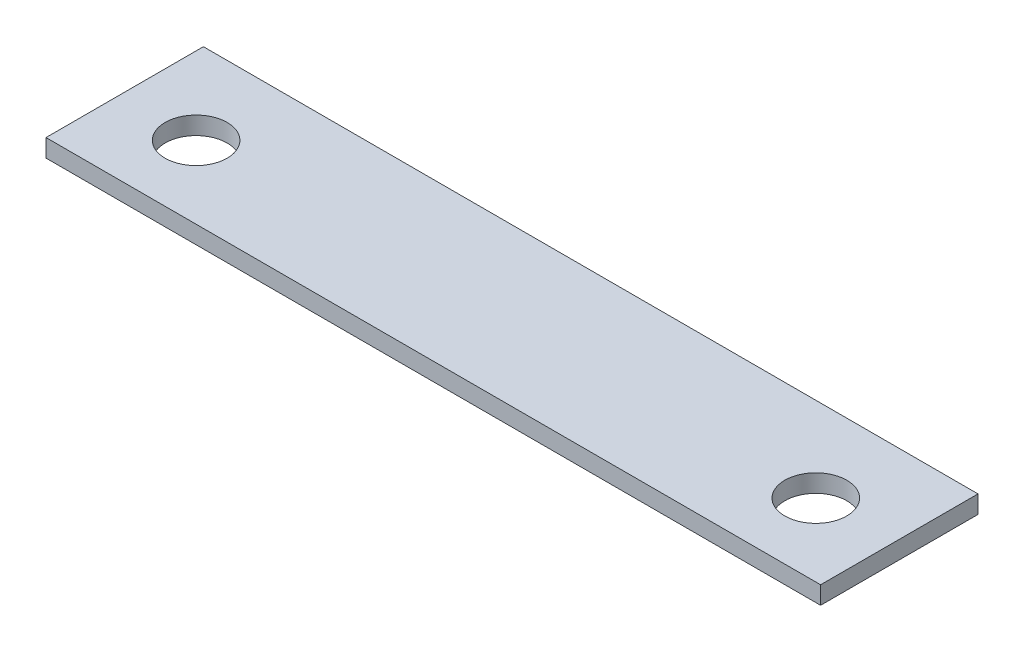
SolidWorks part; units mm, degrees
ref_plane "Front Plane" through (0, 0, 0) normal (0, 0, 1) x (1, 0, 0)
ref_plane "Top Plane" through (0, 0, 0) normal (0, 1, 0) x (1, 0, 0)
ref_plane "Right Plane" through (0, 0, 0) normal (1, 0, 0) x (0, 0, -1)
sketch "Sketch1" plane through (0, 0, 0) normal (0, 1, 0) x (1, 0, 0)
  line L1 (-62.5, 12.7) -> (62.5, 12.7)
  line L2 (-62.5, 12.7) -> (-62.5, -12.7)
  line L3 (-62.5, -12.7) -> (62.5, -12.7)
  line L4 (62.5, 12.7) -> (62.5, -12.7)
  line L5 (-62.5, 12.7) -> (62.5, -12.7) construction
  line L6 (-62.5, -12.7) -> (62.5, 12.7) construction
  point P0 (0, 0)
  dimension "D1" = 25.4
  dimension "D2" = 125
extrude "Boss-Extrude1" add sketch "Sketch1" along normal blind 2.875
sketch "Sketch2" plane through (0, 0, 0) normal (0, -1, 0) x (1, 0, 0)
  circle A0 centre (-50, 0.975) radius 5
  circle A1 centre (50, 0.975) radius 5
extrude "Cut-Extrude1" cut sketch "Sketch2" against normal up to next
